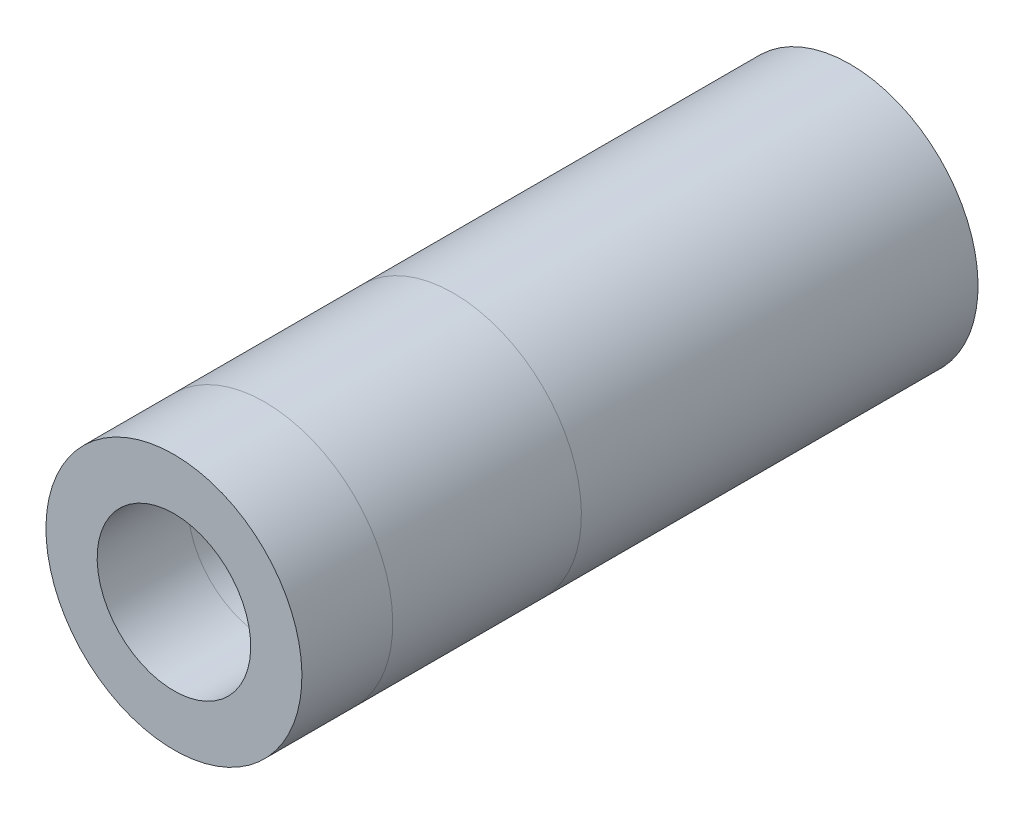
SolidWorks part; units mm, degrees
material "Silicon Rubber"
ref_plane "X-Y Datum" through (0, 0, 0) normal (0, 0, 1) x (1, 0, 0)
ref_plane "X-Z Datum" through (0, 0, 0) normal (0, 1, 0) x (1, 0, 0)
ref_plane "Y-Z Datum" through (0, 0, 0) normal (1, 0, 0) x (0, 0, -1)
sketch3d "3DSketch1"
  line L0 (-46.03, 0, -24.6) -> (-46.03, 0, 0)
  line L1 (-46.03, 0, 0) -> (-46.03, 0, 11.7)
  line L2 (-46.03, 0, 17.3335) -> (-46.03, 0, 11.7)
  arc A0 (-42.0547, 0, 0) -> (-50.0053, 0, 0) centre (-46.03, 0, 0) ccw construction
  arc A1 (-42.0547, 0, 0) -> (-50.0053, 0, 0) centre (-46.03, 0, 0) ccw construction
  arc A2 (-46.03, 5, -24.6) -> (-41.03, 0, -24.6) centre (-46.03, 0, -24.6) ccw construction
  arc A3 (-46.03, 5, -24.6) -> (-41.03, 0, -24.6) centre (-46.03, 0, -24.6) ccw construction
  circle A8 centre (-46.03, 0, 17.3335) radius 5 construction
  circle A9 centre (-46.03, 0, 17.3335) radius 5 construction
  point P3 (-46.03, 0, 3.9753)
  point P4 (-46.03, 0, 3.9753)
  point P8 (-46.03, 0, -29.6)
  point P9 (-46.03, 0, -29.6)
  point P13 (-46.03, 0, 12.3335)
  point P16 (-46.03, 0, 12.3335)
sweep "Sweep1" add path "3DSketch1" circular profile diameter 15.875 parameters "D3"=15.875
sweep "Cut-Sweep1" cut path "3DSketch1<2>" circular profile diameter 9.525 parameters "D3"=9.525
sketch3d "3DSketch1<2>" same geometry as "3DSketch1"
